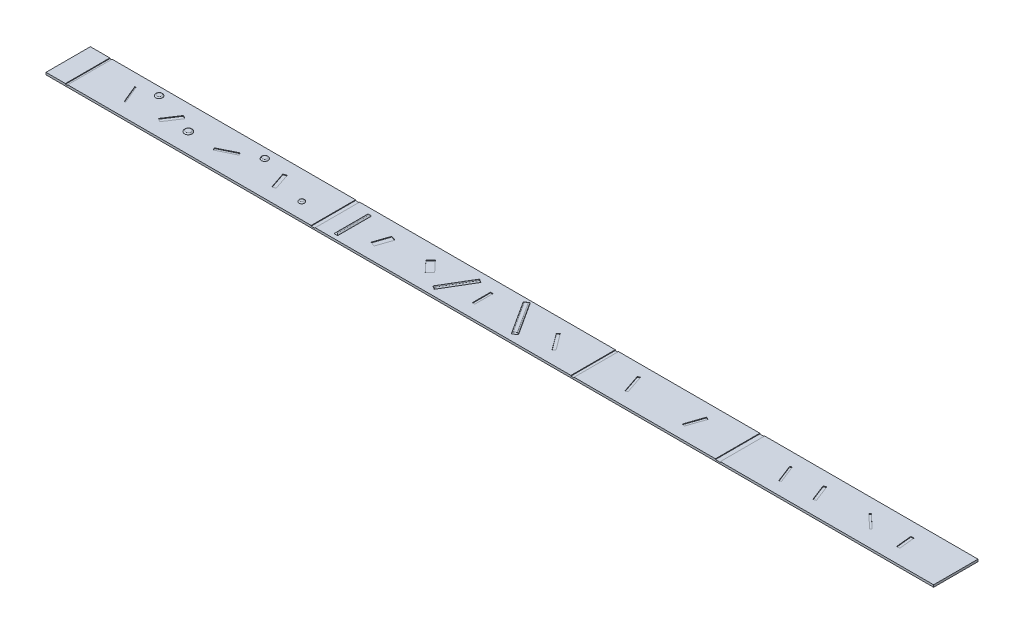
SolidWorks part; units mm, degrees
ref_plane "Alzado" through (0, 0, 0) normal (0, 0, 1) x (1, 0, 0)
ref_plane "Planta" through (0, 0, 0) normal (0, 1, 0) x (1, 0, 0)
ref_plane "Vista lateral" through (0, 0, 0) normal (1, 0, 0) x (0, 0, -1)
sketch "Croquis1" plane through (0, 0, 0) normal (0, 1, 0) x (1, 0, 0)
  line L1 (-20000, 1000) -> (20000, 1000)
  line L2 (-20000, 1000) -> (-20000, -1000)
  line L3 (-20000, -1000) -> (20000, -1000)
  line L4 (20000, 1000) -> (20000, -1000)
  line L5 (-20000, 1000) -> (20000, -1000) construction
  line L6 (-20000, -1000) -> (20000, 1000) construction
  point P0 (0, 0)
  dimension "D1" = 40000
  dimension "D2" = 2000
extrude "Saliente-Extruir1" add sketch "Croquis1" along normal blind 100
sketch "Croquis2" plane through (0, 100, 0) normal (0, 1, 0) x (1, 0, 0)
  line L0 (20000, 1000) -> (-20000, 1000) construction
  line L1 (-19123.9382, 1000) -> (-19023.9382, 1000)
  line L2 (-19123.9382, 1000) -> (-19123.9382, -1000)
  line L3 (-19123.9382, -1000) -> (-19023.9382, -1000)
  line L4 (-19023.9382, 1000) -> (-19023.9382, -1000)
  line L5 (-20000, -1000) -> (20000, -1000) construction
  line L14 (-13200.6123, -266.8851) -> (-12417.2305, 116.8122)
  line L15 (-13200.6123, -266.8851) -> (-13257.0005, -151.7593)
  line L16 (-12417.2305, 116.8122) -> (-12473.6186, 231.938)
  line L17 (-13257.0005, -151.7593) -> (-12473.6186, 231.938)
  line L23 (-8049.6553, -1000) -> (-7868.7781, -1000)
  line L24 (-8049.6553, -1000) -> (-8049.6553, 1000)
  line L25 (-8049.6553, 1000) -> (-7868.7781, 1000)
  line L26 (-7868.7781, -1000) -> (-7868.7781, 1000)
  line L30 (-4111.6032, 231.938) -> (-3644.07, -266.8851)
  line L31 (-4111.6032, 231.938) -> (-3892.0622, 437.7078)
  line L32 (-3644.07, -266.8851) -> (-3424.529, -61.1153)
  line L33 (-3892.0622, 437.7078) -> (-3424.529, -61.1153)
  line L39 (3655.3213, 1000) -> (3799.2174, 1000)
  line L40 (3655.3213, 1000) -> (3655.3213, -1000)
  line L41 (3655.3213, -1000) -> (3799.2174, -1000)
  line L42 (3799.2174, 1000) -> (3799.2174, -1000)
  line L47 (10167.1093, 1000) -> (10386.746, 1000)
  line L48 (10167.1093, 1000) -> (10167.1093, -1000)
  line L49 (10167.1093, -1000) -> (10386.746, -1000)
  line L50 (10386.746, 1000) -> (10386.746, -1000)
  line L54 (-17438.4091, 437.7078) -> (-17093.0981, -388.5005)
  line L55 (-17438.4091, 437.7078) -> (-17389.308, 458.2294)
  line L56 (-17093.0981, -388.5005) -> (-17043.997, -367.9789)
  line L57 (-17389.308, 458.2294) -> (-17043.997, -367.9789)
  line L58 (-15509.7818, -367.9789) -> (-15663.9914, -266.8851)
  line L59 (-15509.7818, -367.9789) -> (-15061.6538, 315.6007)
  line L60 (-15663.9914, -266.8851) -> (-15215.8634, 416.6945)
  line L61 (-15061.6538, 315.6007) -> (-15215.8634, 416.6945)
  line L62 (-10543.6032, 416.6945) -> (-10693.3822, 366.1476)
  line L63 (-10543.6032, 416.6945) -> (-10289.5004, -336.2551)
  line L64 (-10693.3822, 366.1476) -> (-10439.2795, -386.802)
  line L65 (-10289.5004, -336.2551) -> (-10439.2795, -386.802)
  line L66 (-5806.7253, 391.421) -> (-5586.2729, 315.6007)
  line L67 (-5806.7253, 391.421) -> (-6047.5764, -308.8684)
  line L68 (-5586.2729, 315.6007) -> (-5827.124, -384.6888)
  line L69 (-6047.5764, -308.8684) -> (-5827.124, -384.6888)
  line L70 (-1403.439, 437.7078) -> (-1403.439, -384.6888)
  line L71 (-1403.439, 437.7078) -> (-1289.1565, 437.7078)
  line L72 (-1403.439, -384.6888) -> (-1289.1565, -384.6888)
  line L73 (-1289.1565, 437.7078) -> (-1289.1565, -384.6888)
  line L74 (1682.8723, 315.6007) -> (1785.3191, 391.421)
  line L75 (1682.8723, 315.6007) -> (2232.2776, -426.7441)
  line L76 (1785.3191, 391.421) -> (2334.7244, -350.9237)
  line L77 (2232.2776, -426.7441) -> (2334.7244, -350.9237)
  line L78 (5296.7959, 492.3073) -> (5192.5023, 457.1107)
  line L79 (5296.7959, 492.3073) -> (5580.6175, -348.7042)
  line L80 (5192.5023, 457.1107) -> (5476.3239, -383.9009)
  line L81 (5580.6175, -348.7042) -> (5476.3239, -383.9009)
  line L82 (8191.4342, -426.7441) -> (8065.785, -383.9009)
  line L83 (8191.4342, -426.7441) -> (8465.8363, 378.0133)
  line L84 (8065.785, -383.9009) -> (8340.1871, 420.8565)
  line L85 (8465.8363, 378.0133) -> (8340.1871, 420.8565)
  line L86 (12135.0834, 378.0133) -> (12448.464, -426.7441)
  line L87 (12135.0834, 378.0133) -> (12222.2869, 411.9712)
  line L88 (12448.464, -426.7441) -> (12535.6674, -392.7862)
  line L89 (12222.2869, 411.9712) -> (12535.6674, -392.7862)
  line L90 (13771.057, 411.9712) -> (14066.5006, -346.7242)
  line L91 (13771.057, 411.9712) -> (13652.6133, 365.848)
  line L92 (14066.5006, -346.7242) -> (13948.0569, -392.8474)
  line L93 (13652.6133, 365.848) -> (13948.0569, -392.8474)
  line L94 (15767.3425, 315.6007) -> (16382.6253, -266.8851)
  line L95 (15767.3425, 315.6007) -> (15822.3611, 373.7172)
  line L96 (16382.6253, -266.8851) -> (16437.6439, -208.7686)
  line L97 (15822.3611, 373.7172) -> (16437.6439, -208.7686)
  line L98 (17597.9615, 373.7172) -> (17672.1274, -346.7242)
  line L99 (17597.9615, 373.7172) -> (17736.9134, 388.0216)
  line L100 (17672.1274, -346.7242) -> (17811.0792, -332.4198)
  line L101 (17736.9134, 388.0216) -> (17811.0792, -332.4198)
  dimension "D1" = 100
extrude "Cortar-Extruir3" cut sketch "Croquis2" against normal blind 30
sketch "Croquis3" plane through (0, 100, 0) normal (0, 1, 0) x (1, 0, 0)
  circle A0 centre (-16527.7466, 627.6907) radius 152.1084
  circle A1 centre (-14473.6235, -112.749) radius 170.3882
  circle A2 centre (-11694.9842, 556.0353) radius 149.5871
  circle A3 centre (-9187.0432, -283.1372) radius 124.0966
extrude "Saliente-Extruir2" add sketch "Croquis3" along normal blind 50
fillet "Redondeo1" radius 50 4 edges at (-9187.0432, 150, 407.2337) (-11694.9842, 150, -406.4482) (-14473.6235, 150, 283.1372) (-16527.7466, 150, -475.5823)
sketch "Croquis4" plane through (0, 100, 0) normal (0, 1, 0) x (1, 0, 0)
  line L0 (-2782.8397, -722.0882) -> (-1999.4067, 596.3722)
  line L1 (-7196.8158, 711.0209) -> (-7053.5049, 711.0209)
  line L2 (-7196.8158, 711.0209) -> (-7196.8158, -808.0748)
  line L3 (-7196.8158, -808.0748) -> (-7053.5049, -808.0748)
  line L4 (-7053.5049, 711.0209) -> (-7053.5049, -808.0748)
  line L5 (-2782.8397, -722.0882) -> (-2918.1242, -641.7018)
  line L6 (-1999.4067, 596.3722) -> (-2134.6912, 676.7586)
  line L7 (-2918.1242, -641.7018) -> (-2134.6912, 676.7586)
  line L8 (-270.1217, 768.3453) -> (694.8384, -722.0882)
  line L9 (-270.1217, 768.3453) -> (-76.0551, 893.991)
  line L10 (694.8384, -722.0882) -> (888.905, -596.4425)
  line L11 (-76.0551, 893.991) -> (888.905, -596.4425)
extrude "Saliente-Extruir3" add sketch "Croquis4" along normal blind 50
fillet "Redondeo2" radius 50 12 edges at (406.425, 150, -148.7742) (791.8717, 150, 659.2654) (212.3583, 150, -23.1285) (-173.0884, 150, -831.1681) (-2526.4077, 150, -17.5284) (-2067.049, 150, -636.5654) (-2391.1232, 150, 62.858) (-2850.4819, 150, 681.895) (-7125.1604, 150, -711.0209) (-7053.5049, 150, 48.5269) (-7125.1604, 150, 808.0748) (-7196.8158, 150, 48.5269)
